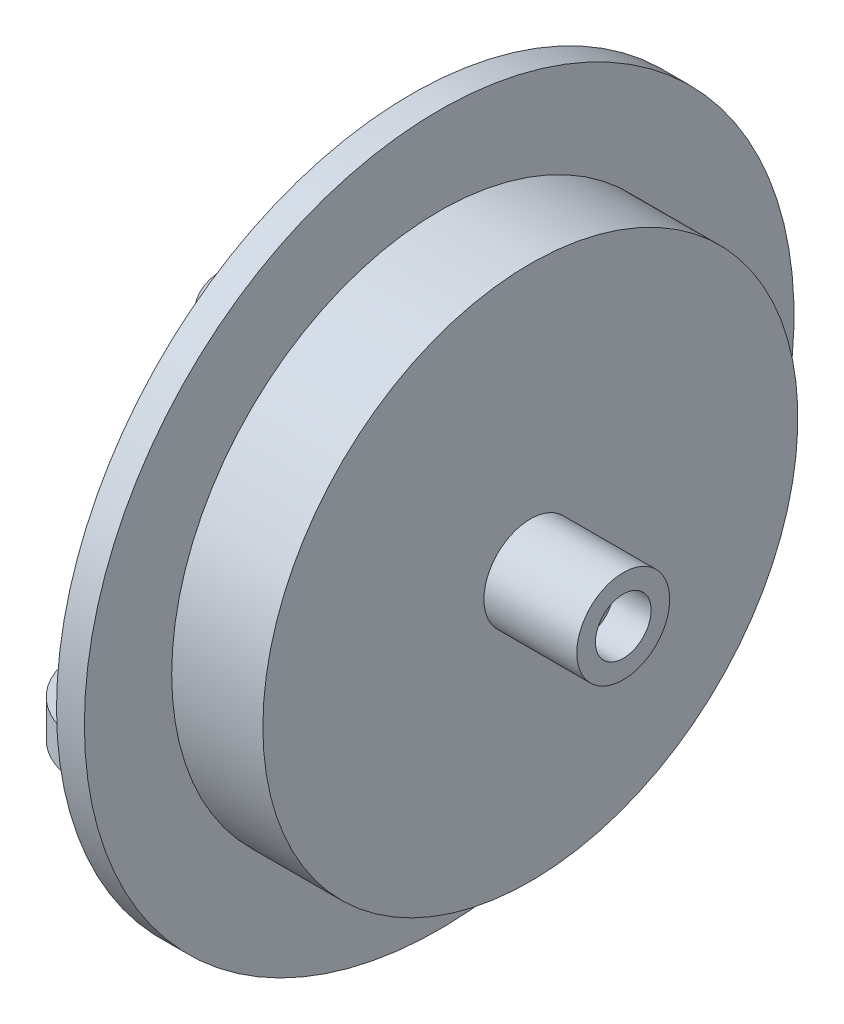
SolidWorks part; units mm, degrees
ref_plane "Front Plane" through (0, 0, 0) normal (0, 0, 1) x (1, 0, 0)
ref_plane "Top Plane" through (0, 0, 0) normal (0, 1, 0) x (1, 0, 0)
ref_plane "Right Plane" through (0, 0, 0) normal (1, 0, 0) x (0, 0, -1)
sketch "Sketch1" plane through (0, 0, 0) normal (0, 1, 0) x (1, 0, 0)
  line L0 (-25.5271, 0) -> (28.1622, 0) construction
  line L1 (0, 2.5) -> (0, 14.4)
  line L2 (0, 14.4) -> (-4.908, 14.4)
  line L3 (-4.908, 14.4) -> (-4.908, 19.1)
  line L4 (-4.908, 19.1) -> (-6.408, 19.1)
  line L5 (-6.408, 19.1) -> (-6.408, 0)
  line L6 (-6.408, 0) -> (0, 0)
  line L7 (0, 2.5) -> (5, 2.5)
  line L8 (5, 2.5) -> (5, 0)
  line L9 (5, 0) -> (0, 0)
  point P14 (-3.3335, 10.1501)
  dimension "D1" = 28.8
  dimension "D2" = 1.5
  dimension "D3" = 38.2
  dimension "D4" = 5
  dimension "D5" = 5
revolve "Revolve1" add sketch "Sketch1" angle 360 about L0
sketch "Sketch2" plane through (-6.408, 0, 0) normal (-1, 0, 0) x (0, 0, 1)
  circle A0 centre (0, 0) radius 1
  dimension "D1" = 2
extrude "Cut-Extrude1" cut sketch "Sketch2" against normal through all
sketch "Sketch3" plane through (5, 0, 0) normal (1, 0, 0) x (0, 0, -1)
  circle A0 centre (0, 0) radius 1.5
  dimension "D1" = 3
extrude "Cut-Extrude2" cut sketch "Sketch3" against normal blind 2
sketch "Sketch4" plane through (-6.408, 0, 0) normal (-1, 0, 0) x (0, 0, 1)
  line L0 (0, 19.1) -> (0, -19.1) construction
  line L1 (-4, 6) -> (4, 6)
  line L2 (-4, 6) -> (-4, 4)
  line L3 (-4, 4) -> (4, 4)
  line L4 (4, 6) -> (4, 4)
  line L5 (-4, -4) -> (4, -4)
  line L6 (-4, -4) -> (-4, -6)
  line L7 (-4, -6) -> (4, -6)
  line L8 (4, -4) -> (4, -6)
  line L9 (-19.1, 0) -> (19.1, 0) construction
  circle A0 centre (0, 0) radius 19.1 construction
  dimension "D1" = 8
  dimension "D2" = 8
  dimension "D3" = 2
  dimension "D4" = 2
  dimension "D5" = 8
  dimension "D6" = 4
  dimension "D8" = 4
extrude "Boss-Extrude1" add sketch "Sketch4" along normal blind 10
sketch "Sketch6" plane through (0, 6, 0) normal (0, 1, 0) x (1, 0, 0)
  line L0 (-6.408, -4) -> (-6.408, 4) construction
  circle A0 centre (-11.408, 0) radius 2.5 construction
  circle A1 centre (-11.408, 0) radius 1.25
  dimension "D1" = 5
  dimension "D3" = 2.5
  dimension "D2" = 5
extrude "Cut-Extrude4" cut sketch "Sketch6" against normal blind 20
fillet "Fillet1" radius 4 4 edges at (-16.408, -5, 4) (-16.408, -5, -4) (-16.408, 5, 4) (-16.408, 5, -4)
sketch "Sketch7" plane through (0, 0, 4) normal (0, 0, 1) x (1, 0, 0)
  line L8 (-6.408, -4) -> (-12.408, -4)
  line L9 (-12.408, -4) -> (-12.408, -6)
  line L10 (-12.408, -6) -> (-6.408, -6)
  line L11 (-6.408, -6) -> (-6.408, -4)
  line L12 (-6.408, -4) -> (-12.408, -4)
  line L13 (-12.408, -4) -> (-12.408, -6)
  line L14 (-12.408, -6) -> (-6.408, -6)
  line L15 (-6.408, -6) -> (-6.408, -4)
  dimension "D1" = 0
extrude "Boss-Extrude2" add sketch "Sketch7" along normal blind 12
sketch "Sketch8" plane through (0, -4, 0) normal (0, 1, 0) x (1, 0, 0)
  line L0 (-12.408, -16) -> (-12.408, -4) construction
  line L1 (-6.408, -16) -> (-12.408, -16) construction
  circle A0 centre (-9.408, -13) radius 1.25
  dimension "D1" = 2.5
  dimension "D2" = 3
  dimension "D3" = 3
extrude "Cut-Extrude5" cut sketch "Sketch8" against normal blind 12
fillet "Fillet2" radius 4 1 edges at (-12.408, -5, 16)
